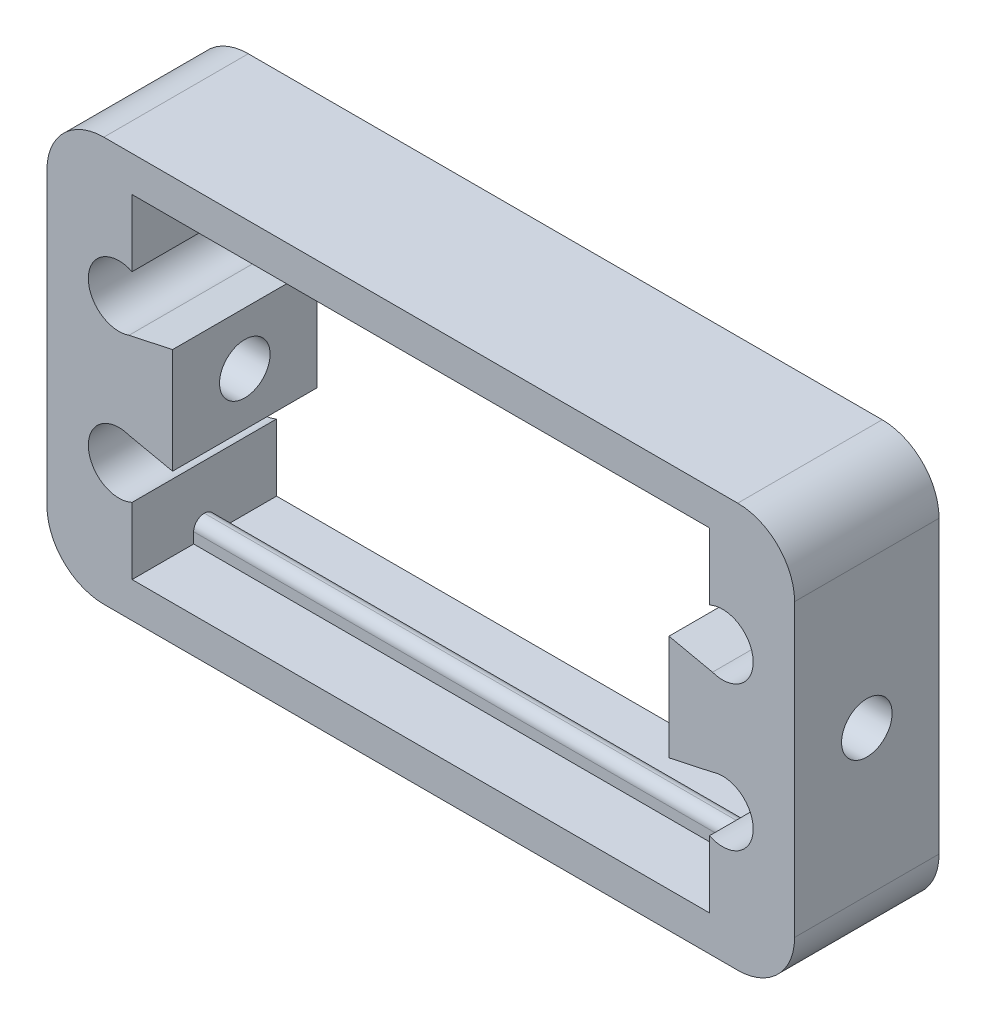
SolidWorks part; units mm, degrees
ref_plane "Front Plane" through (0, 0, 0) normal (0, 0, 1) x (1, 0, 0)
ref_plane "Top Plane" through (0, 0, 0) normal (0, 1, 0) x (1, 0, 0)
ref_plane "Right Plane" through (0, 0, 0) normal (1, 0, 0) x (0, 0, -1)
sketch "Sketch1" plane through (0, 0, 0) normal (0, 0, 1) x (1, 0, 0)
  line L0 (2.4892, 9.652) -> (2.4892, 14.224) construction
  line L1 (0, 0) -> (26.289, 0)
  line L2 (0, 0) -> (0, 14.224)
  line L3 (0, 14.224) -> (26.289, 14.224)
  line L4 (26.289, 0) -> (26.289, 14.224)
  line L5 (2.4892, 4.572) -> (2.4892, 0) construction
  line L6 (13.1445, 14.224) -> (13.1445, 0) construction
  line L7 (2.9942, 12.974) -> (23.2948, 12.974)
  line L8 (23.2948, 12.974) -> (23.2948, 10.624)
  line L9 (2.9942, 1.25) -> (2.9942, 3.6)
  line L10 (21.8715, 8.9642) -> (21.8715, 5.2598)
  line L11 (21.8715, 8.9642) -> (23.4023, 8.634)
  line L12 (0, 7.112) -> (26.289, 7.112) construction
  line L13 (21.8715, 5.2598) -> (23.4023, 5.59)
  line L14 (2.9942, 1.25) -> (23.2948, 1.25)
  line L15 (23.2948, 1.25) -> (23.2948, 3.6)
  line L16 (4.4175, 5.2598) -> (2.8867, 5.59)
  line L17 (4.4175, 8.9642) -> (4.4175, 5.2598)
  line L18 (4.4175, 8.9642) -> (2.8867, 8.634)
  line L19 (2.9942, 12.974) -> (2.9942, 10.624)
  circle A0 centre (2.4892, 9.652) radius 0.889
  circle A1 centre (2.4892, 4.572) radius 0.889
  circle A2 centre (23.7998, 4.572) radius 0.889
  circle A3 centre (23.7998, 9.652) radius 0.889
  arc A4 (23.2948, 10.624) -> (23.4023, 8.634) centre (23.7564, 9.651) cw
  arc A5 (23.2948, 3.6) -> (23.4023, 5.59) centre (23.7564, 4.573) ccw
  arc A6 (2.9942, 3.6) -> (2.8867, 5.59) centre (2.5326, 4.573) cw
  arc A7 (2.9942, 10.624) -> (2.8867, 8.634) centre (2.5326, 9.651) ccw
  dimension "D3" = 1.778
  dimension "D4" = 1.778
  dimension "D1" = 26.289
  dimension "D2" = 14.224
  dimension "D5" = 5.08
  dimension "D6" = 21.3106
  dimension "D7" = 1.25
  dimension "D8" = 2.35
extrude "Boss-Extrude1" add sketch "Sketch1" along normal blind 5.08 contours L1 L4 L3 L2 A7 L19 L7 L8 A4 L11 L10 L13 A5 L15 L14 L9 A6 L16 L17 L18 region at (0.2989, 7.112, 0)
ref_plane "Plane1" through (0, 0, 2.54) normal (0, 0, 1) x (1, 0, 0)
sketch "Sketch2" plane through (0, 0, 2.54) normal (0, 0, 1) x (1, 0, 0)
  line L0 (2.9942, 1.25) -> (2.9942, 3.6) construction
  line L1 (2.9942, 2) -> (23.2948, 2)
  line L2 (2.9942, 2) -> (2.9942, 1.25)
  line L3 (2.9942, 1.25) -> (23.2948, 1.25)
  line L4 (23.2948, 2) -> (23.2948, 1.25)
  line L5 (0, 7.112) -> (26.289, 7.112) construction
  line L6 (0, 0) -> (0, 14.224) construction
  line L7 (26.289, 0) -> (26.289, 14.224) construction
  line L8 (23.2948, 12.224) -> (23.2948, 12.974)
  line L9 (2.9942, 12.974) -> (23.2948, 12.974)
  line L10 (2.9942, 12.224) -> (2.9942, 12.974)
  line L11 (2.9942, 12.224) -> (23.2948, 12.224)
  dimension "D1" = 0.75
extrude "Boss-Extrude2" add sketch "Sketch2" along normal blind 0.375 and the other way blind 0.375
fillet "Fillet1" radius 0.375 4 edges at (13.1445, 12.224, 2.165) (13.1445, 12.224, 2.915) (13.1445, 2, 2.165) (13.1445, 2, 2.915)
fillet "Fillet2" radius 2 4 edges at (26.289, 14.224, 2.54) (26.289, 0, 2.54) (0, 14.224, 2.54) (0, 0, 2.54)
sketch "Sketch3" plane through (26.289, 0, 0) normal (1, 0, 0) x (0, 0, -1)
  circle A0 centre (-2.54, 7.112) radius 0.889
  dimension "D1" = 1.778
extrude "Cut-Extrude1" cut sketch "Sketch3" against normal blind 24.13
